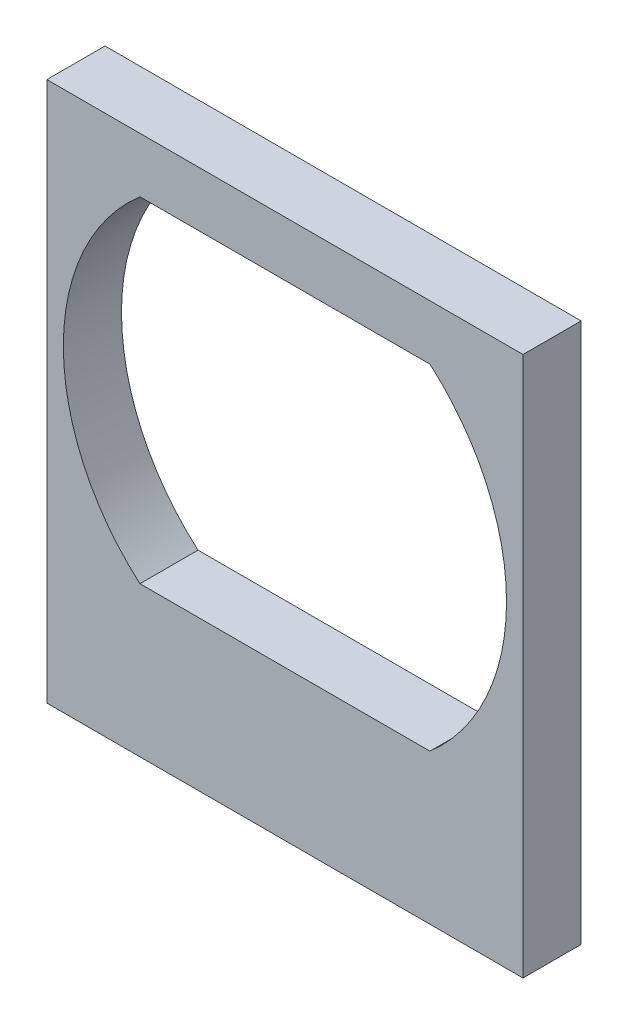
SolidWorks part; units mm, degrees
ref_plane "Front Plane" through (0, 0, 0) normal (1, 0, 0) x (0, 1, 0)
ref_plane "Top Plane" through (0, 0, 0) normal (0, 0, 1) x (0, 1, 0)
ref_plane "Right Plane" through (0, 0, 0) normal (0, 1, 0) x (-1, 0, 0)
sketch "Sketch1" plane through (0, 0, 0) normal (0, 0, 1) x (0, 1, 0)
  line L2 (-9.15, 7.9175) -> (-9.15, -7.9175)
  line L4 (9.15, 7.9175) -> (9.15, -7.9175)
  arc A0 (9.15, 7.9175) -> (-9.15, 7.9175) centre (0, 0) ccw
  arc A1 (-9.15, -7.9175) -> (9.15, -7.9175) centre (0, 0) ccw
  circle A2 centre (0, 0) radius 1.03 construction
  point P7 (9.15, 0)
  dimension "D3" = 24.2
  dimension "D2" = 2.06
  dimension "D1" = 18.3
sketch "Sketch2" plane through (0, 0, 0) normal (0, 0, 1) x (0, 1, 0)
  line L1 (-17.337, 13) -> (12.15, 13)
  line L2 (-17.337, 13) -> (-17.337, -13)
  line L3 (-17.337, -13) -> (12.15, -13)
  line L4 (12.15, 13) -> (12.15, -13)
  line L5 (9.15, 7.9175) -> (9.15, -7.9175) construction
  point P6 (12.15, 0)
  dimension "D1" = 26
  dimension "D2" = 3
  dimension "D3" = 17.337
extrude "Boss-Extrude1" add sketch "Sketch2" along normal blind 3.175
extrude "Cut-Extrude1" cut sketch "Sketch1" along normal through all
hole_wizard "Tap Drill for M3x0.5 Tap1" positions "Sketch3" profile "Sketch4" hole size "M3x0.5" standard "ANSI Metric"
sketch "Sketch3" plane through (0, -17.337, 0) normal (0, -1, 0) x (-1, 0, 0)
  line L0 (-7.5, -1.5875) -> (7.5, -1.5875) construction
  line L2 (13, 0) -> (-13, 0) construction
  line L3 (13, -3.175) -> (-13, -3.175) construction
  point P0 (-7.5, -1.5875)
  point P2 (7.5, -1.5875)
  point P9 (0, -1.5875)
  point P15 (-7.7252, -3.25)
  dimension "D1" = 15
sketch "Sketch4" plane through (7.5, -17.337, 1.5875) normal (1, 0, 0) x (0, 0, -1)
  line L0 (0, 0) -> (0, 6.7511)
  line L1 (0, 6.7511) -> (1.25, 6)
  line L2 (1.25, 6) -> (1.25, 0.025)
  line L3 (1.25, 0.025) -> (1.275, 0)
  line L5 (1.275, 0) -> (0, 0)
  line L6 (-1.25, 0.025) -> (-1.275, 0) construction
  line L10 (0, 6.7511) -> (-1.25, 6) construction
  line L11 (0, -6.35) -> (0, 107.95) construction
  dimension "Hole Dia." = 2.5
  dimension "Hole Depth" = 6
  dimension "Near C'Sink Dia." = 2.55
  dimension "Near C'Sink Angle" = 90
  dimension "Drill Angle" = 118
